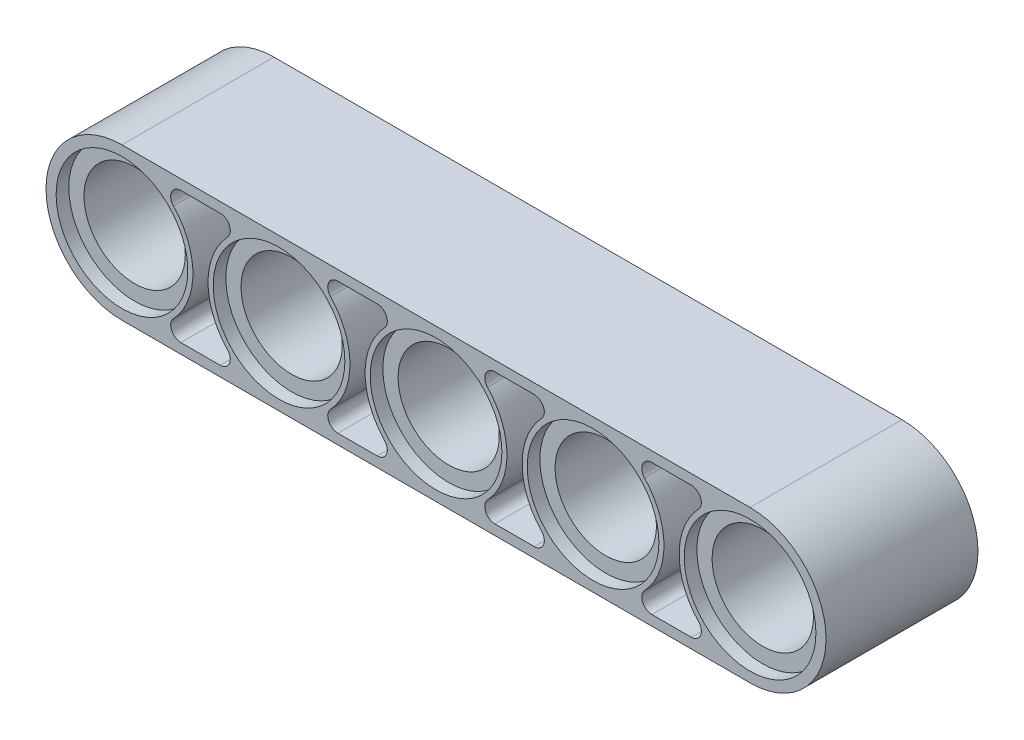
SolidWorks part; units mm, degrees
material "PVC Rigid"
ref_plane "Front Plane" through (0, 0, 0) normal (0, 0, 1) x (1, 0, 0)
ref_plane "Top Plane" through (0, 0, 0) normal (0, 1, 0) x (1, 0, 0)
ref_plane "Right Plane" through (0, 0, 0) normal (1, 0, 0) x (0, 0, -1)
sketch "Sketch1" plane through (0, 0, 0) normal (0, 0, 1) x (1, 0, 0)
  line L0 (-7.874, 0) -> (7.874, 0) construction
  line L1 (7.874, -3.81) -> (-7.874, -3.81)
  line L2 (7.874, 3.81) -> (-7.874, 3.81)
  line L8 (0, 15.1379) -> (0, -14.3507)
  line L9 (3.937, 3.302) -> (3.937, -3.302) construction
  line L10 (3.937, 3.302) -> (3.937, 3.81)
  line L11 (2.9512, -3.302) -> (4.9228, -3.302)
  line L12 (2.9512, 3.302) -> (4.9228, 3.302)
  line L13 (3.937, -3.302) -> (3.937, -3.81)
  line L14 (-3.937, 3.302) -> (-3.937, -3.302) construction
  line L15 (-3.937, -3.302) -> (-3.937, -3.81)
  line L16 (-2.9512, 3.302) -> (-4.9228, 3.302)
  line L17 (-2.9512, -3.302) -> (-4.9228, -3.302)
  line L18 (-3.937, 3.302) -> (-3.937, 3.81)
  arc A0 (7.874, -3.81) -> (7.874, 3.81) centre (7.874, 0) ccw
  circle A1 centre (0, 0) radius 3.302
  circle A2 centre (0, 0) radius 2.54
  circle A3 centre (7.874, 0) radius 3.302
  circle A4 centre (7.874, 0) radius 2.54
  arc A5 (-2.9512, 3.302) -> (-2.5823, 2.4447) centre (-2.9512, 2.794) cw
  arc A7 (-4.9228, 3.302) -> (-5.2917, 2.4447) centre (-4.9228, 2.794) ccw
  arc A8 (-5.2917, -2.4447) -> (-4.9228, -3.302) centre (-4.9228, -2.794) ccw
  arc A11 (2.5823, -2.4448) -> (2.5823, 2.4447) centre (0, 0) ccw
  arc A12 (5.2917, 2.4447) -> (5.2917, -2.4447) centre (7.874, 0) ccw
  arc A13 (2.5823, -2.4448) -> (2.9512, -3.302) centre (2.9512, -2.794) ccw
  arc A14 (-2.5823, -2.4448) -> (-2.9512, -3.302) centre (-2.9512, -2.794) cw
  arc A15 (-5.2917, 2.4447) -> (-5.2917, -2.4447) centre (-7.874, 0) cw
  arc A16 (5.2917, -2.4447) -> (4.9228, -3.302) centre (4.9228, -2.794) cw
  arc A17 (4.9228, 3.302) -> (5.2917, 2.4447) centre (4.9228, 2.794) cw
  arc A18 (2.9512, 3.302) -> (2.5823, 2.4447) centre (2.9512, 2.794) ccw
  arc A19 (-2.5823, -2.4448) -> (-2.5823, 2.4447) centre (0, 0) cw
  circle A20 centre (-7.874, 0) radius 2.54
  circle A21 centre (-7.874, 0) radius 3.302
  arc A22 (-7.874, -3.81) -> (-7.874, 3.81) centre (-7.874, 0) cw
  point P13 (9.525, 0)
  point P14 (0, -3.81)
  point P15 (7.62, 0)
  point P17 (0, 3.302)
  point P18 (19.05, 3.302)
  point P19 (0, -3.302)
  point P20 (19.05, -3.302)
  point P23 (13.843, 0)
  point P25 (23.368, 0)
  point P26 (3.429, 0)
  point P27 (-7.874, -3.302)
  point P28 (7.874, -3.302)
  point P29 (-7.874, 3.302)
  point P30 (7.874, 3.302)
  point P35 (11.811, 0)
  point P60 (11.5175, 1.1139)
  point P67 (0, 3.81)
  dimension "D2" = 7.62
  dimension "D3" = 0.508
  dimension "D4" = 5.08
  dimension "D6" = 11.684
  dimension "D1" = 0.254
  dimension "D5" = 0.508
extrude "Boss-Extrude1" add sketch "Sketch1" along normal blind 3.81 contours A3 A4 | L12 A17 A12 A16 L11 A0 A3 region at (5.9055, -3.7013, 0) region at (4.6654, 0, 0)
ref_plane "Plane2" through (11.684, 0, 0) normal (1, 0, 0) x (0, 0, -1)
extrude "Boss-Extrude2" add sketch "Sketch1<7>" along normal blind 3.81 separate body contours L8 A1 | A2 L8 A1 | A18 L12 L8 A1 L11 A13 A11 | A2 L8 A1 region at (1.9685, -3.7242, 0) region at (-1.9685, -3.7242, 0) region at (-3.2282, 0, 0) region at (0.0738, -2.921, 0)
sketch "Sketch1<7>" plane through (0, 0, 0) normal (0, 0, 1) x (1, 0, 0) same geometry as "Sketch1"
sketch "Sketch2" plane through (0, 0, 0) normal (0, 0, 1) x (1, 0, 0)
  circle A0 centre (7.874, 0) radius 3.302 construction
  circle A1 centre (0, 0) radius 3.302 construction
  circle A2 centre (7.874, 0) radius 3.302
  circle A3 centre (0, 0) radius 3.302
extrude "Cut-Extrude1" cut sketch "Sketch2" along normal blind 0.635
pattern_linear "LPattern1" count 3 spacing 7.874 along (-1, 0, 0) of "Boss-Extrude2", "Cut-Extrude1"
ref_plane "Plane1" through (-7.874, 0, 0) normal (1, 0, 0) x (0, 0, -1)
mirror "Mirror2" about plane through (-7.874, 0, 0) normal (1, 0, 0) of bodies 109 101
combine bodies "Combine1" operation type add bodies to combine 109 106 107
ref_plane "Plane3" through (0, 0, 3.81) normal (0, 0, 1) x (1, 0, 0)
mirror "Mirror3" about plane through (0, 0, 3.81) normal (0, 0, 1) of bodies 108
ref_plane "Plane4" through (-27.432, 0, 0) normal (-1, 0, 0) x (0, 0, 1)
